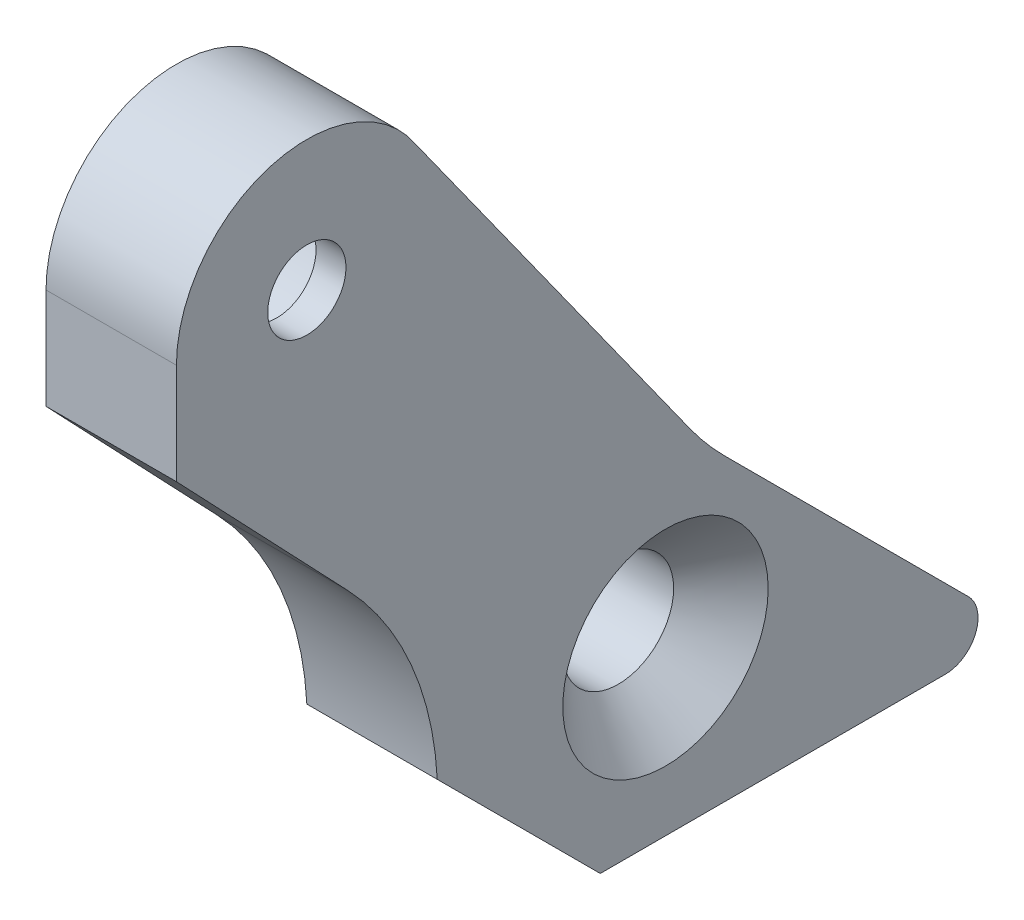
SolidWorks part; units mm, degrees
ref_plane "Plano frontal" through (0, 0, 0) normal (0, 0, 1) x (1, 0, 0)
ref_plane "Plano superior" through (0, 0, 0) normal (0, 1, 0) x (1, 0, 0)
ref_plane "Plano direito" through (0, 0, 0) normal (1, 0, 0) x (0, 0, -1)
sketch "Esboço1" plane through (0, 0, 0) normal (1, 0, 0) x (0, 0, -1)
  line L0 (0, 0) -> (0, 3.0918)
  line L1 (7.362, 5.2591) -> (16.226, -7.1341)
  line L10 (0, 0) -> (8, -8.3993)
  line L11 (8, -8.3993) -> (8, -11.9082)
  line L12 (13, -16.9082) -> (26, -16.9082)
  line L13 (26, -16.9082) -> (16.226, -7.1341)
  line L14 (8, -11.9082) -> (13, -16.9082)
  arc A0 (0, 3.0918) -> (7.362, 5.2591) centre (4, 3.0918) cw
  dimension "D1" = 4
  dimension "D3" = 45
  dimension "D2" = 8
  dimension "D6" = 20
  dimension "D7" = 22
  dimension "D8" = 5
  dimension "D9" = 5
extrude "Ressalto-extrusão1" add sketch "Esboço1" along normal blind 4
hole_wizard "Furo de diâmetro Ø6.0 (6)1" positions "Esboço2" profile "Esboço3" hole size "Ø6.0" standard "ISO"
sketch "Esboço2" plane through (0, 0, 0) normal (-1, 0, 0) x (0, 0, 1)
  arc A0 (0, 3.0918) -> (-7.362, 5.2591) centre (-4, 3.0918) ccw construction
  point P0 (-4, 3.0918)
sketch "Esboço3" plane through (0, 3.0918, -4) normal (0, 1, 0) x (0, 0, 1)
  line L0 (0, 0) -> (0, 3.8026)
  line L1 (0, 3.8026) -> (3, 2)
  line L2 (3, 2) -> (3, 0)
  line L5 (3, 0) -> (0, 0)
  line L10 (0, 3.8026) -> (-3, 2) construction
  line L11 (0, -6.35) -> (0, 107.95) construction
  dimension "Hole Dia." = 6
  dimension "Hole Depth" = 2
  dimension "Drill Angle" = 118
sketch "Esboço4" plane through (4, 0, 0) normal (1, 0, 0) x (0, 0, -1)
  circle A0 centre (4, 3.0918) radius 1.2
  arc A2 (7.362, 5.2591) -> (0, 3.0918) centre (4, 3.0918) ccw construction
  dimension "D1" = 2.4
extrude "Corte-extrusão1" cut sketch "Esboço4" against normal through all
hole_wizard "Escareado para parafuso com cabeça escareada chata de M31" positions "Esboço5" profile "Esboço6" countersink size "M3" standard "ISO" end condition through all
sketch "Esboço5" plane through (4, 0, 0) normal (1, 0, 0) x (0, 0, -1)
  line L0 (13, -16.9082) -> (26, -16.9082) construction
  line L1 (8, -8.3993) -> (8, -11.9082) construction
  point P0 (15, -11.9082)
  dimension "D1" = 5
  dimension "D2" = 7
sketch "Esboço6" plane through (4, -11.9082, -15) normal (0, 1, 0) x (0, 0, -1)
  line L0 (0, 0) -> (0, 4)
  line L1 (0, 4) -> (1.7, 4)
  line L2 (1.7, 4) -> (1.7, 1.45)
  line L3 (1.7, 1.45) -> (3.15, 0)
  line L5 (3.15, 0) -> (0, 0)
  line L6 (-1.7, 1.45) -> (-3.15, 0) construction
  line L11 (0, -6.35) -> (0, 107.95) construction
  dimension "Thru Hole Dia." = 3.4
  dimension "Thru Hole Depth" = 4
  dimension "Near C'Sink Dia." = 6.3
  dimension "Near C'Sink Angle" = 90
fillet "Filete1" radius 10 2 edges at (2, -8.3993, -8) (2, -7.1341, -16.226)
fillet "Filete2" radius 1 1 edges at (2, -16.9082, -26)
